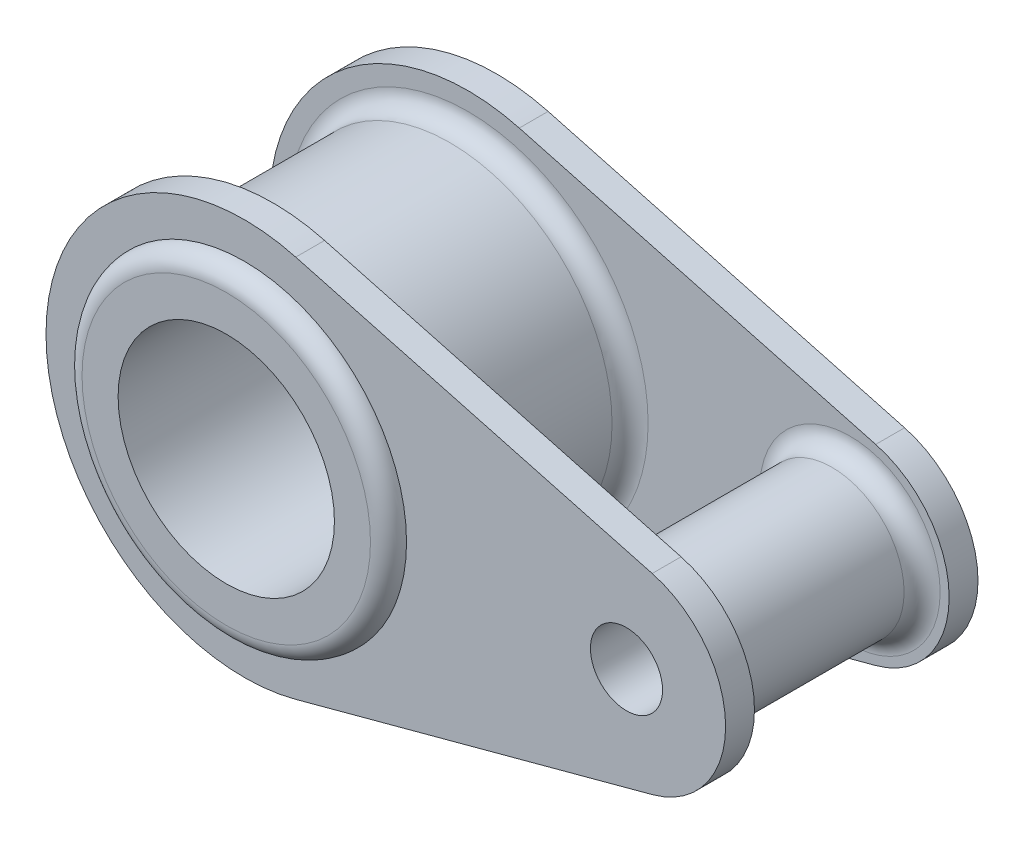
SolidWorks part; units mm, degrees
ref_plane "前视基准面" through (0, 0, 0) normal (0, 0, 1) x (1, 0, 0)
ref_plane "上视基准面" through (0, 0, 0) normal (0, 1, 0) x (1, 0, 0)
ref_plane "右视基准面" through (0, 0, 0) normal (1, 0, 0) x (0, 0, -1)
other "Configuration Table"
sketch "草图1" plane through (0, 0, 0) normal (0, 0, 1) x (1, 0, 0)
  line L0 (0, 55) -> (0, -64.6914) construction
  line L1 (0, 0) -> (24.6343, 0) construction
  line L2 (14.2689, 53.1168) -> (113.1344, 26.5584)
  line L3 (14.2689, -53.1168) -> (113.1344, -26.5584)
  circle A0 centre (0, 0) radius 30
  circle A1 centre (0, 0) radius 45
  circle A2 centre (0, 0) radius 55
  circle A3 centre (106, 0) radius 10
  circle A4 centre (106, 0) radius 27.5
  dimension "D2" = 110
  dimension "D3" = 90
  dimension "D4" = 60
  dimension "D5" = 20
  dimension "D6" = 55
  dimension "D1" = 106
extrude "凸台-拉伸1" add sketch "草图1" along normal blind 80 contours A1 A0 region at (-43.7272, 0, 0)
fillet "圆角1" radius 5 2 edges at (45, 0, 0) (45, 0, 80)
extrude "凸台-拉伸4" add sketch "草图1<6>" along normal blind 8 from offset 5 contours A2 A1 | A4 L2 A2 L3 | A4 A3 region at (65.7958, 0, 0) region at (42.4106, 32.5214, 0) region at (127.2053, 16.2607, 0)
sketch "草图1<6>" plane through (0, 0, 0) normal (0, 0, 1) x (1, 0, 0) same geometry as "草图1"
sketch "草图3" plane through (0, 0, 80) normal (0, 0, 1) x (1, 0, 0)
  line L2 (14.2689, -53.1168) -> (113.1344, -26.5584)
  line L3 (113.1344, 26.5584) -> (14.2689, 53.1168)
  line L4 (14.2689, -53.1168) -> (113.1344, -26.5584)
  line L5 (113.1344, 26.5584) -> (14.2689, 53.1168)
  circle A0 centre (106, 0) radius 10 construction
  circle A1 centre (106, 0) radius 10
  arc A2 (14.2689, 53.1168) -> (14.2689, -53.1168) centre (0, 0) ccw
  arc A3 (113.1344, -26.5584) -> (113.1344, 26.5584) centre (106, 0) ccw
  arc A4 (14.2689, 53.1168) -> (14.2689, -53.1168) centre (0, 0) ccw
  arc A5 (113.1344, -26.5584) -> (113.1344, 26.5584) centre (106, 0) ccw
  circle A6 centre (0, 0) radius 30 construction
  circle A7 centre (0, 0) radius 30
  dimension "D1" = 0
extrude "凸台-拉伸7" add sketch "草图3" against normal blind 8 from offset 5 offset against normal yes
sketch "草图4" plane through (0, 0, 5) normal (0, 0, -1) x (-1, 0, 0)
  circle A0 centre (-106, 0) radius 10 construction
  circle A1 centre (-106, 0) radius 10
  circle A2 centre (-106, 0) radius 20
  dimension "D1" = 40
sketch "草图5" plane through (0, 0, 5) normal (0, 0, -1) x (-1, 0, 0)
  circle A0 centre (-106, 0) radius 10
  circle A1 centre (-106, 0) radius 20
extrude "凸台-拉伸9" add sketch "草图4" along direction (0, 0, 1) on the side against the normal blind 70 contours A2
extrude "切除-拉伸1" cut sketch "草图5" against normal through all both and the other way through all contours A0
fillet "圆角2" radius 5 4 edges at (45, 0, 13) (45, 0, 67) (126, 0, 13) (126, 0, 67)
